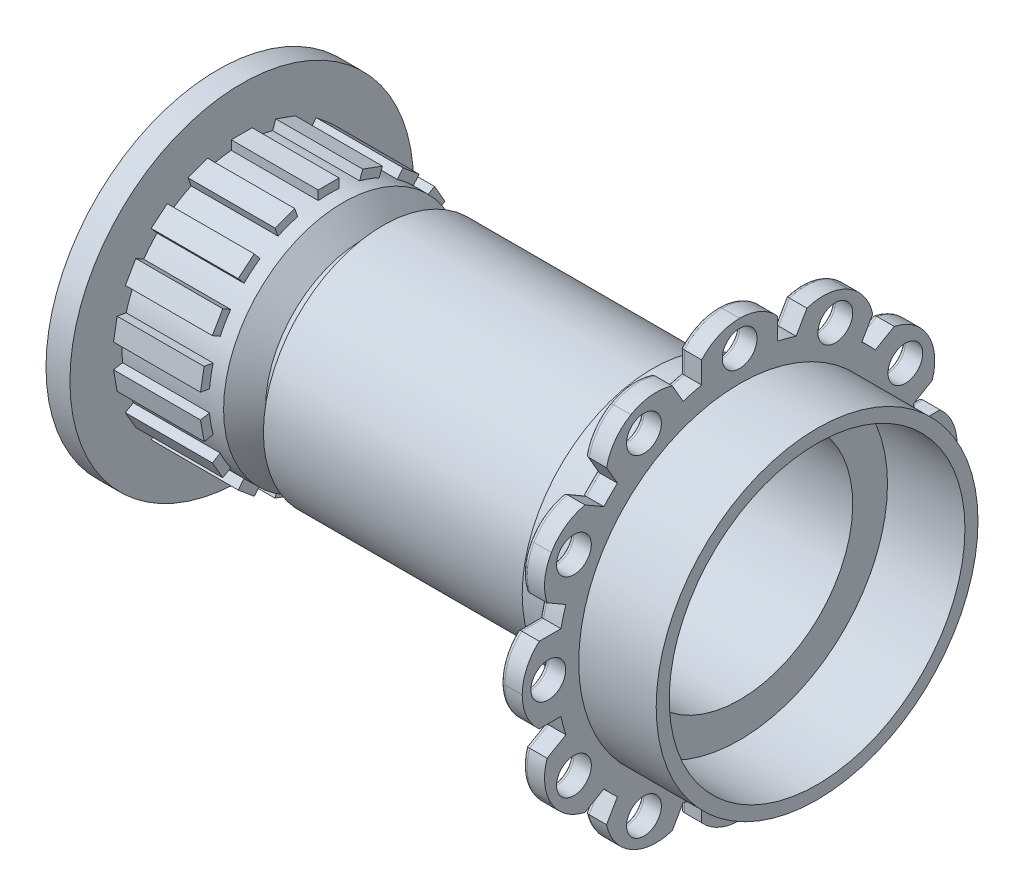
SolidWorks part; units mm, degrees
material "AISI 4130 Steel, annealed at 865C"
ref_plane "Front Plane" through (0, 0, 0) normal (0, 0, 1) x (1, 0, 0)
ref_plane "Top Plane" through (0, 0, 0) normal (0, 1, 0) x (1, 0, 0)
ref_plane "Right Plane" through (0, 0, 0) normal (1, 0, 0) x (0, 0, -1)
sketch "Sketch1" plane through (0, 0, 0) normal (0, 0, 1) x (1, 0, 0)
  line L0 (0, 0) -> (0, 9.842) construction
  line L1 (-5, 0) -> (-5, 30)
  line L2 (-5, 30) -> (-20, 30)
  line L3 (-20, 30) -> (-20, 27.5)
  line L4 (-20, 27.5) -> (-82.01, 27.5)
  line L5 (-82.01, 27.5) -> (-82.01, 22.25)
  line L6 (-82.01, 22.25) -> (-86.76, 22.25)
  line L7 (-86.76, 22.25) -> (-91.1653, 27.5)
  line L8 (-91.1653, 27.5) -> (-106.1653, 27.5)
  line L12 (-106.1653, 27.5) -> (-114.5, 27.5)
  line L13 (-114.5, 27.5) -> (-114.5, 0)
  line L14 (-114.5, 0) -> (-5, 0)
  point P17 (0, 50)
  point P19 (-51.005, 27.5)
  dimension "D1" = 50
  dimension "D2" = 5
  dimension "D3" = 15
  dimension "D4" = 30
  dimension "D5" = 27.5
  dimension "D6" = 22.25
  dimension "D7" = 32.49
  dimension "D8" = 114.5
  dimension "D10" = 15
  dimension "D12" = 130
  dimension "D13" = 4.75
revolve "Revolve1" add sketch "Sketch1" angle 360 about L14
sketch "Sketch2" plane through (-5, 0, 0) normal (1, 0, 0) x (0, 0, -1)
  line L0 (0, 0) -> (0, 38.31) construction
  line L1 (0, 0) -> (-8.7323, 41.0822) construction
  line L2 (0, 38.31) -> (0, 50) construction
  line L3 (-8.7323, 41.0822) -> (-8.7323, 46.0822)
  line L4 (0, 0) -> (8.7323, 41.0822) construction
  line L5 (8.7323, 41.0822) -> (8.7323, 46.0822)
  line L6 (12.9787, 39.9444) -> (15.4787, 44.2745)
  line L7 (28.1035, 31.2121) -> (30.6035, 35.5422)
  line L8 (31.2121, 28.1035) -> (35.5422, 30.6035)
  line L9 (39.9444, 12.9787) -> (44.2745, 15.4787)
  line L10 (41.0822, 8.7323) -> (46.0822, 8.7323)
  line L11 (41.0822, -8.7323) -> (46.0822, -8.7323)
  line L12 (39.9444, -12.9787) -> (44.2745, -15.4787)
  line L13 (31.2121, -28.1035) -> (35.5422, -30.6035)
  line L14 (28.1035, -31.2121) -> (30.6035, -35.5422)
  line L15 (12.9787, -39.9444) -> (15.4787, -44.2745)
  line L16 (8.7323, -41.0822) -> (8.7323, -46.0822)
  line L17 (-8.7323, -41.0822) -> (-8.7323, -46.0822)
  line L18 (-12.9787, -39.9444) -> (-15.4787, -44.2745)
  line L19 (-28.1035, -31.2121) -> (-30.6035, -35.5422)
  line L20 (-31.2121, -28.1035) -> (-35.5422, -30.6035)
  line L21 (-39.9444, -12.9787) -> (-44.2745, -15.4787)
  line L22 (-41.0822, -8.7323) -> (-46.0822, -8.7323)
  line L23 (-41.0822, 8.7323) -> (-46.0822, 8.7323)
  line L24 (-39.9444, 12.9787) -> (-44.2745, 15.4787)
  line L25 (-31.2121, 28.1035) -> (-35.5422, 30.6035)
  line L26 (-28.1035, 31.2121) -> (-30.6035, 35.5422)
  line L27 (-12.9787, 39.9444) -> (-15.4787, 44.2745)
  arc A0 (-8.7323, 41.0822) -> (-12.9787, 39.9444) centre (0, 0) ccw
  arc A1 (-8.7323, 46.0822) -> (0, 50) centre (-0.0002, 38.31) cw
  arc A2 (8.7323, 46.0822) -> (0, 50) centre (0.0002, 38.31) ccw
  arc A3 (15.4787, 44.2745) -> (25, 43.3013) centre (19.1548, 33.1775) cw
  arc A4 (30.6035, 35.5422) -> (25, 43.3013) centre (19.1552, 33.1773) ccw
  arc A5 (35.5422, 30.6035) -> (43.3013, 25) centre (33.1773, 19.1552) cw
  arc A6 (44.2745, 15.4787) -> (43.3013, 25) centre (33.1775, 19.1548) ccw
  arc A7 (46.0822, 8.7323) -> (50, 0) centre (38.31, 0.0002) cw
  arc A8 (46.0822, -8.7323) -> (50, 0) centre (38.31, -0.0002) ccw
  arc A9 (44.2745, -15.4787) -> (43.3013, -25) centre (33.1775, -19.1548) cw
  arc A10 (35.5422, -30.6035) -> (43.3013, -25) centre (33.1773, -19.1552) ccw
  arc A11 (30.6035, -35.5422) -> (25, -43.3013) centre (19.1552, -33.1773) cw
  arc A12 (15.4787, -44.2745) -> (25, -43.3013) centre (19.1548, -33.1775) ccw
  arc A13 (8.7323, -46.0822) -> (0, -50) centre (0.0002, -38.31) cw
  arc A14 (-8.7323, -46.0822) -> (0, -50) centre (-0.0002, -38.31) ccw
  arc A15 (-15.4787, -44.2745) -> (-25, -43.3013) centre (-19.1548, -33.1775) cw
  arc A16 (-30.6035, -35.5422) -> (-25, -43.3013) centre (-19.1552, -33.1773) ccw
  arc A17 (-35.5422, -30.6035) -> (-43.3013, -25) centre (-33.1773, -19.1552) cw
  arc A18 (-44.2745, -15.4787) -> (-43.3013, -25) centre (-33.1775, -19.1548) ccw
  arc A19 (-46.0822, -8.7323) -> (-50, 0) centre (-38.31, -0.0002) cw
  arc A20 (-46.0822, 8.7323) -> (-50, 0) centre (-38.31, 0.0002) ccw
  arc A21 (-44.2745, 15.4787) -> (-43.3013, 25) centre (-33.1775, 19.1548) cw
  arc A22 (-35.5422, 30.6035) -> (-43.3013, 25) centre (-33.1773, 19.1552) ccw
  arc A23 (-30.6035, 35.5422) -> (-25, 43.3013) centre (-19.1552, 33.1773) cw
  arc A24 (-15.4787, 44.2745) -> (-25, 43.3013) centre (-19.1548, 33.1775) ccw
  arc A25 (-28.1035, 31.2121) -> (-31.2121, 28.1035) centre (0, 0) ccw
  arc A26 (12.9787, 39.9444) -> (8.7323, 41.0822) centre (0, 0) ccw
  arc A27 (31.2121, 28.1035) -> (28.1035, 31.2121) centre (0, 0) ccw
  arc A28 (41.0822, 8.7323) -> (39.9444, 12.9787) centre (0, 0) ccw
  arc A29 (39.9444, -12.9787) -> (41.0822, -8.7323) centre (0, 0) ccw
  arc A30 (28.1035, -31.2121) -> (31.2121, -28.1035) centre (0, 0) ccw
  arc A31 (8.7323, -41.0822) -> (12.9787, -39.9444) centre (0, 0) ccw
  arc A32 (-12.9787, -39.9444) -> (-8.7323, -41.0822) centre (0, 0) ccw
  arc A33 (-31.2121, -28.1035) -> (-28.1035, -31.2121) centre (0, 0) ccw
  arc A34 (-41.0822, -8.7323) -> (-39.9444, -12.9787) centre (0, 0) ccw
  arc A35 (-39.9444, 12.9787) -> (-41.0822, 8.7323) centre (0, 0) ccw
  point P92 (0, 0)
  dimension "D2" = 84
  dimension "D6" = 11.69
  dimension "D1" = 38.31
  dimension "D3" = 12
  dimension "D4" = 11.69
  dimension "D5" = 5
  dimension "D7" = 12
extrude "Boss-Extrude1" add sketch "Sketch2" along normal blind 5
sketch "Sketch3" plane through (0, 0, 0) normal (1, 0, 0) x (0, 0, -1)
  line L0 (0, 0) -> (0, 44) construction
  circle A0 centre (0, 44) radius 4
  dimension "D2" = 8
  dimension "D1" = 44
extrude "Cut-Extrude2" cut sketch "Sketch3" against normal blind 5
pattern_circular "CirPattern1" count 12 over 360 about axis through (-114.5, 0, 0) along (-1, 0, 0) of "Cut-Extrude2"
fillet "Fillet1" radius 1 73 edges at (-5, 42.1094, 14.2287) (-5, 44.8069, 20.3435) (-5, 40.0215, 28.6322) (-5, 33.3771, 29.3535) (-5, 29.6985, 29.6985) (-5, 29.3535, 33.3771) (-5, 28.6322, 40.0215) (-5, 20.3435, 44.8069) (-5, 14.2287, 42.1094) (-5, 10.8704, 40.5689) (-5, 8.7323, 43.5822) (-5, 4.7855, 48.9757) (-5, -4.7855, 48.9757) (-5, -8.7323, 43.5822) (-5, -10.8704, 40.5689) (-5, -14.2287, 42.1094) (-5, -20.3435, 44.8069) (-5, -28.6322, 40.0215) (-5, -29.3535, 33.3771) (-5, -29.6985, 29.6985) (-5, -33.3771, 29.3535) (-5, -40.0215, 28.6322) (-5, -44.8069, 20.3435) (-5, -42.1094, 14.2287) (-5, -40.5689, 10.8704) (-5, -43.5822, 8.7323) (-5, -48.9757, 4.7855) (-5, -48.9757, -4.7855) (-5, -43.5822, -8.7323) (-5, -40.5689, -10.8704) (-5, -42.1094, -14.2287) (-5, -44.8069, -20.3435) (-5, -40.0215, -28.6322) (-5, -33.3771, -29.3535) (-5, -29.6985, -29.6985) (-5, -29.3535, -33.3771) (-5, -28.6322, -40.0215) (-5, -20.3435, -44.8069) (-5, -14.2287, -42.1094) (-5, -10.8704, -40.5689) (-5, -8.7323, -43.5822) (-5, -4.7855, -48.9757) (-5, 4.7855, -48.9757) (-5, 8.7323, -43.5822) (-5, 10.8704, -40.5689) (-5, 14.2287, -42.1094) (-5, 20.3435, -44.8069) (-5, 28.6322, -40.0215) (-5, 29.3535, -33.3771) (-5, 29.6985, -29.6985) (-5, 33.3771, -29.3535) (-5, 40.0215, -28.6322) (-5, 44.8069, -20.3435) (-5, 42.1094, -14.2287) (-5, 40.5689, -10.8704) (-5, 43.5822, -8.7323) (-5, 48.9757, -4.7855) (-5, 48.9757, 4.7855) (-5, 43.5822, 8.7323) (-5, 40.5689, 10.8704) (-5, 0, -30) (-5, 44, -4) (-5, 36.1051, -25.4641) (-5, 40.1051, 18.5359) (-5, 25.4641, 36.1051) (-5, 4, 44) (-5, -18.5359, 40.1051) (-5, -36.1051, 25.4641) (-5, -44, 4) (-5, -40.1051, -18.5359) (-5, -25.4641, -36.1051) (-5, -4, -44) (-5, 18.5359, -40.1051)
sketch "Sketch5" plane through (0, 0, 0) normal (1, 0, 0) x (0, 0, -1)
  circle A0 centre (0, 0) radius 37
  circle A1 centre (0, 0) radius 34
  dimension "D1" = 74
  dimension "D2" = 68
extrude "Boss-Extrude2" add sketch "Sketch5" along normal blind 17.81
sketch "Sketch6" plane through (0, 0, 0) normal (0, 0, 1) x (1, 0, 0)
  line L0 (0, 0) -> (0, 26)
  line L2 (0, 26) -> (-63, 26)
  line L3 (-63, 26) -> (-63, 14)
  line L4 (-63, 14) -> (-111.5, 14)
  line L5 (-111.5, 14) -> (-111.5, 20)
  line L6 (-111.5, 20) -> (-114.5, 20)
  line L7 (-114.5, 20) -> (-114.5, 0)
  line L8 (-114.5, 0) -> (0, 0)
  line L9 (-114.5, 27.5) -> (-114.5, -27.5) construction
  dimension "D1" = 26
  dimension "D2" = 63
  dimension "D3" = 14
  dimension "D4" = 48.5
  dimension "D5" = 20
revolve "Cut-Revolve2" cut sketch "Sketch6" angle 360 about L8
chamfer "Chamfer1" distance 11 angle 45 1 edges at (-63, -26, 0)
sketch "Sketch7" plane through (-114.5, 0, 0) normal (-1, 0, 0) x (0, 0, 1)
  line L0 (0, 0) -> (0, 27.5) construction
  line L1 (2.4, 26) -> (-2.4, 26)
  line L2 (-2.4, 26) -> (-2.4, 29.5)
  line L3 (-2.4, 29.5) -> (2.4, 29.5)
  line L4 (2.4, 26) -> (2.4, 29.5)
  circle A0 centre (0, 0) radius 27.5 construction
  point P12 (0, 29.5)
  point P13 (0, 26)
  dimension "D1" = 26
  dimension "D2" = 3.5
  dimension "D3" = 2.4
extrude "Boss-Extrude3" add sketch "Sketch7" against normal blind 20
pattern_circular "CirPattern2" count 18 over 360 of "Boss-Extrude3"
sketch "Sketch8" plane through (-111.5, 0, 0) normal (-1, 0, 0) x (0, 0, 1)
  line L0 (0, 0) -> (0, 15.4) construction
  line L1 (1.2, 15.4) -> (-1.2, 15.4)
  line L2 (-1.2, 15.4) -> (-1.2, 13)
  line L3 (-1.2, 13) -> (1.2, 13)
  line L4 (1.2, 15.4) -> (1.2, 13)
  point P7 (0, 13)
  dimension "D1" = 13
  dimension "D2" = 2.4
  dimension "D3" = 1.2
extrude "Cut-Extrude3" cut sketch "Sketch8" against normal up to surface (48.5 mm away) and the other way blind 20 up to face at (-63, 15, 0)
pattern_circular "CirPattern3" count 15 over 360 about axis through (-114.5, 0, 0) along (-1, 0, 0) of "Cut-Extrude3"
sketch "Sketch10" plane through (0, 0, 0) normal (0, 0, 1) x (1, 0, 0)
  line L0 (-114.5, 29.5) -> (-114.5, 39.5)
  line L1 (-114.5, 39.5) -> (-120, 39.5)
  line L2 (-120, 39.5) -> (-120, 20)
  line L3 (-120, 20) -> (-114.5, 20)
  line L4 (-114.5, 20) -> (-114.5, 29.5)
  line L5 (0, 0) -> (-120, 0) construction
  dimension "D1" = 10
  dimension "D2" = 5.5
revolve "Revolve3" add sketch "Sketch10" angle 360 about L5
